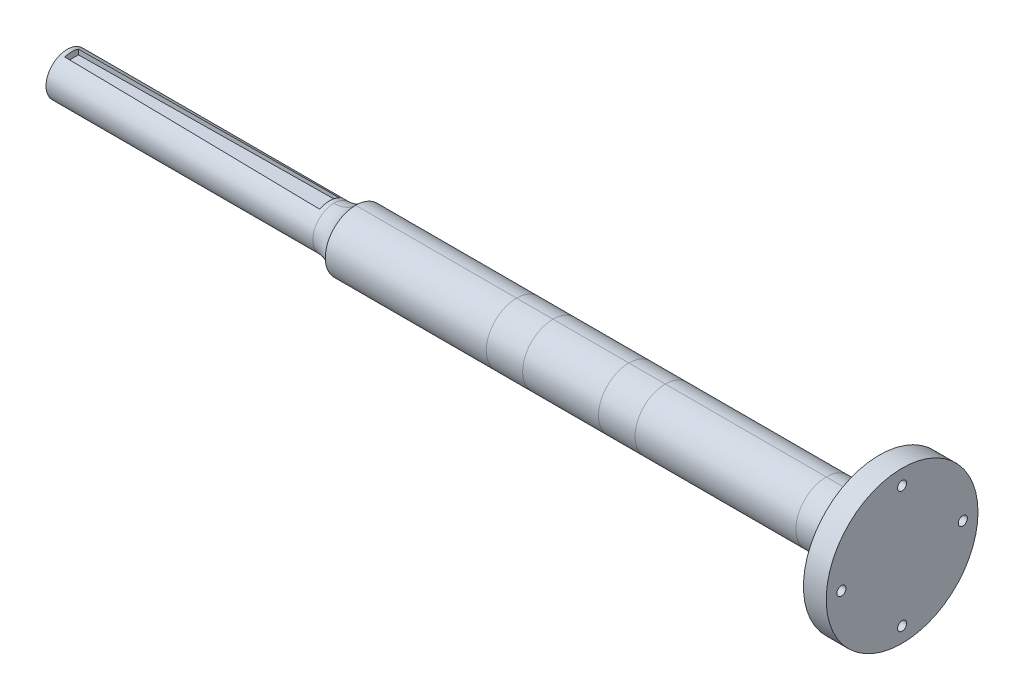
SolidWorks part; units mm, degrees
material "1023 Carbon Steel Sheet (SS)"
ref_plane "Front Plane" through (0, 0, 0) normal (0, 0, 1) x (1, 0, 0)
ref_plane "Top Plane" through (0, 0, 0) normal (0, 1, 0) x (1, 0, 0)
ref_plane "Right Plane" through (0, 0, 0) normal (1, 0, 0) x (0, 0, -1)
sketch "Sketch1" plane through (0, 0, 0) normal (1, 0, 0) x (0, 0, -1)
  circle A0 centre (0, 0) radius 10
  dimension "D1" = 20
extrude "Boss-Extrude1" add sketch "Sketch1" against normal blind 275
sketch "Sketch2" plane through (0, 0, 0) normal (0, 1, 0) x (1, 0, 0)
  line L0 (-127, -10) -> (-127, 10)
  line L1 (-275, -10) -> (0, -10) construction
  line L2 (0, 10) -> (-275, 10) construction
  line L3 (-78, -10) -> (-78, 10)
  line L5 (-275, -10) -> (0, -10) construction
  line L6 (0, 10) -> (-275, 10) construction
  line L7 (-115, -10) -> (-115, 10)
  line L8 (-90, -10) -> (-90, 10)
  line L10 (-25, 10) -> (-25, -10)
  line L11 (0, 10) -> (-275, 10) construction
  line L13 (-10, 10) -> (-10, -10)
  line L14 (-275, -10) -> (0, -10) construction
  line L15 (0, -10) -> (0, 10) construction
  line L16 (0, 0) -> (-275, 0)
  line L17 (-275, 10) -> (-275, -10) construction
  dimension "D1" = 78
  dimension "D2" = 15
  dimension "D3" = 25
  dimension "D4" = 12
  dimension "D5" = 12
  dimension "D6" = 10
split line "Split Line1"
sketch "Sketch3" plane through (-275, 0, 0) normal (-1, 0, 0) x (0, 0, 1)
  circle A0 centre (0, 0) radius 7
  circle A1 centre (0, 0) radius 10
  dimension "D1" = 14
  dimension "D2" = 20
extrude "Cut-Extrude1" cut sketch "Sketch3" against normal blind 95
fillet "Fillet1" radius 10 1 edges at (-180, 0, 7)
sketch "Sketch4" plane through (0, 0, 0) normal (1, 0, 0) x (0, 0, -1)
  circle A0 centre (0, 0) radius 25
  circle A1 centre (0, 0) radius 20 construction
  circle A3 centre (0, 20) radius 1.5
  circle A4 centre (20, 0) radius 1.5
  circle A5 centre (0, -20) radius 1.5
  circle A6 centre (-20, 0) radius 1.5
  point P15 (0, 0)
  dimension "D1" = 50
  dimension "D2" = 40
  dimension "D3" = 3
  dimension "D4" = 4
extrude "Boss-Extrude2" add sketch "Sketch4" against normal blind 7.5
fillet "Fillet3" radius 2.5 2 edges at (-7.5, 0, -10) (-7.5, 0, 10)
ref_plane "Plane1" through (0, 7, 0) normal (0, 1, 0) x (1, 0, 0)
sketch "Sketch9" plane through (0, 7, 0) normal (0, 1, 0) x (1, 0, 0)
  line L0 (-273.5707, 0) -> (-188.5707, 0) construction
  line L3 (-275, 7) -> (-187.1414, 7) construction
  line L4 (-273.5707, -2.25) -> (-273.5707, 2.25)
  line L5 (-273.5707, 2.25) -> (-188.5707, 3.25)
  line L6 (-188.5707, 3.25) -> (-188.5707, -3.25)
  line L7 (-273.5707, -2.25) -> (-188.5707, -3.25)
  point P3 (-231.0707, 0)
  point P6 (-231.0707, 7)
  dimension "D1" = 85
  dimension "D2" = 2.25
  dimension "D3" = 3.25
extrude "Cut-Extrude2" cut sketch "Sketch9" against normal blind 2 contours L5 L6 L7 L4
